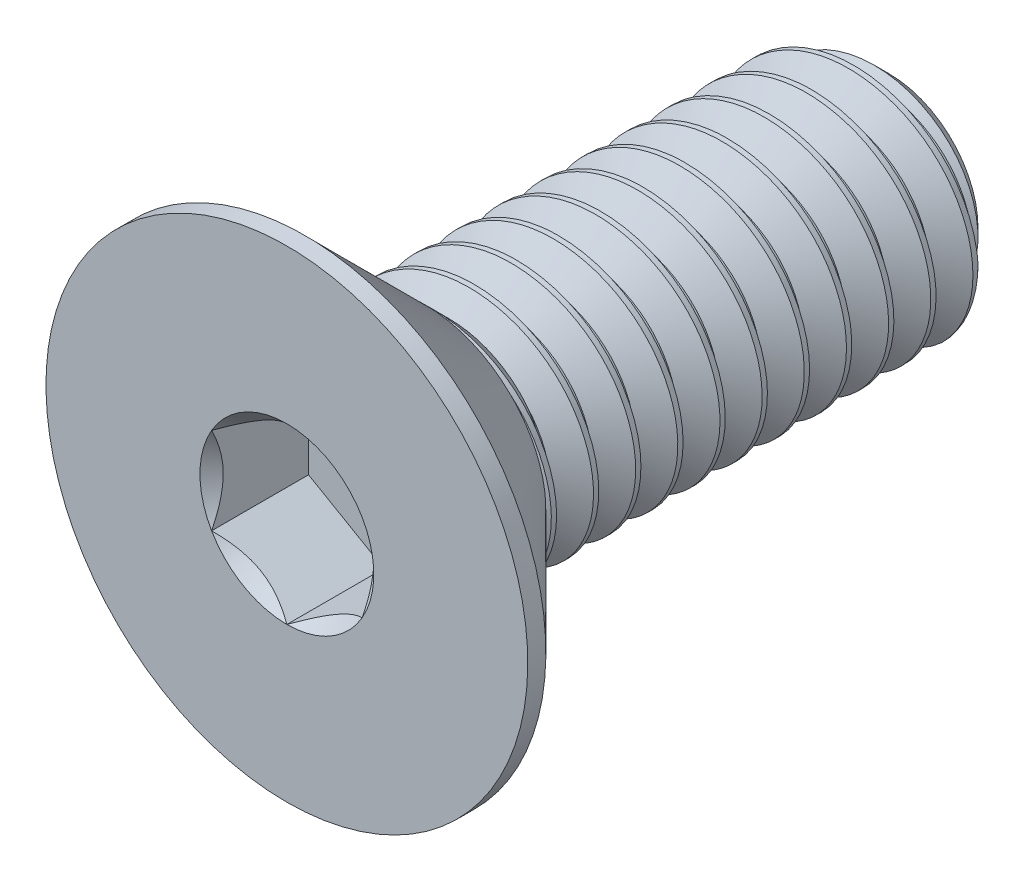
SolidWorks part; units mm, degrees
ref_plane "Front" through (0, 0, 0) normal (0, 0, 1) x (1, 0, 0)
ref_plane "Top" through (0, 0, 0) normal (0, 1, 0) x (1, 0, 0)
ref_plane "Right" through (0, 0, 0) normal (1, 0, 0) x (0, 0, -1)
sketch "Sketch1" plane through (0, 0, 0) normal (1, 0, 0) x (0, 0, -1)
  line L0 (0, 4) -> (0.3, 4) construction
  line L1 (0.3, 4) -> (2.3, 2) construction
  line L2 (0, 2) -> (10, 2)
  line L3 (10, 2) -> (10, 0)
  line L4 (10, 0) -> (0, 0)
  line L5 (0, 0) -> (0, 4) construction
  line L6 (0, 4) -> (0, -4) construction
  line L7 (10, 2) -> (10, -2) construction
  line L8 (0, -4) -> (0.3, -4) construction
  line L9 (0.3, -4) -> (2.3, -2) construction
  line L11 (0, 2) -> (0, 0)
  line L12 (2.3, 2) -> (2.3, 0) construction
revolve "Revolve1" add sketch "Sketch1" angle 360 mid plane about L4
sketch "Sketch3" plane through (0, 0, -10) normal (0, 0, -1) x (-1, 0, 0)
  circle A0 centre (0, 0) radius 2
curve "Helix/Spiral1" pitch 0.7 height 10 radius 2 centre (0, 0, -10) axis (0, 0, 1) start towards (0, 1, 0)
sketch "Sketch2" plane through (0, 0, 0) normal (1, 0, 0) x (0, 0, -1)
  line L0 (10, 2) -> (10.6125, 2)
  line L1 (10.6125, 2) -> (10.35, 1.5453)
  line L2 (10.35, 1.5453) -> (10.2625, 1.5453)
  line L3 (10.2625, 1.5453) -> (10, 2)
  line L4 (10.1312, 1.7727) -> (10.4812, 1.7727) construction
  dimension "D1" = 60
  dimension "D2" = 0.0875
  dimension "D3" = 0.35
chamfer "Chamfer1" distance 0.525 angle 45 1 edges at (0, 2, -10)
sweep "Cut-Sweep1" cut profiles "Sketch2" path "Helix/Spiral1"
sketch "Sketch7" plane through (0, 0, 0) normal (1, 0, 0) x (0, 0, -1)
  line L0 (0, 4) -> (0.3, 4) construction
  line L1 (0.3, 4) -> (2.3, 2) construction
  line L2 (0, 4) -> (0.3, 4)
  line L3 (0.3, 4) -> (2.3, 2)
  line L4 (2.3, 2) -> (2.3, 0) construction
  line L5 (2.3, 2) -> (2.3, 0)
  line L7 (0, 0) -> (0, 4) construction
  line L8 (0, 0) -> (0, 4)
  line L9 (0, 0) -> (2.3, 0)
  line L10 (4.4, 0) -> (-4.4, 0) construction
revolve "Revolve2" add sketch "Sketch7" angle 360 mid plane about L9
ref_plane "Plane1" through (0, 0, -2.3) normal (0, 0, 1) x (1, 0, 0)
sketch "Sketch8" plane through (0, 0, -2.3) normal (0, 0, 1) x (1, 0, 0)
  circle A0 centre (0, 0) radius 2
extrude "Boss-Extrude1" add sketch "Sketch8" against normal through all draft 45
sketch "Sketch5" plane through (0, 0, 0) normal (0, 0, 1) x (1, 0, 0)
  line L1 (1.25, -0.7217) -> (1.25, 0.7217)
  line L2 (1.25, 0.7217) -> (0, 1.4434)
  line L3 (0, 1.4434) -> (-1.25, 0.7217)
  line L4 (-1.25, 0.7217) -> (-1.25, -0.7217)
  line L5 (-1.25, -0.7217) -> (0, -1.4434)
  line L6 (0, -1.4434) -> (1.25, -0.7217)
  circle A0 centre (0, 0) radius 1.25 construction
  dimension "Hex" = 2.5
extrude "Cut-Extrude2" cut sketch "Sketch5" against normal blind 1.61
sketch "Sketch6" plane through (0, 0, 0) normal (0, 0, 1) x (1, 0, 0)
  circle A0 centre (0, 0) radius 1.4434
extrude "Cut-Extrude3" cut sketch "Sketch6" against normal blind 1.61 draft 45
sketch "Sketch9" [suppressed] plane through (0, 0, -1.5) normal (0, 0, 1) x (1, 0, 0)
  circle A1 centre (0, 0) radius 1.25
  circle A2 centre (0, 0) radius 1.25
  point P0 (0, 1.25)
  dimension "D1" = 0
extrude "Boss-Extrude2" [suppressed] add sketch "Sketch9" against normal offset from surface (3.5 mm away) 26 up to face at (0, 1.475, -10)
fillet "Fillet1" [suppressed] radius 0.4
sketch "Sketch10" plane through (0, 0, 0) normal (1, 0, 0) x (0, 0, -1)
  line L0 (10, 2) -> (10, -2) construction
  point P0 (8.95, -2)
  dimension "D1" = 1.05
equation "\"D3@Helix/Spiral1\" = \"Lg@Sketch1\""
equation "\"D2@Sketch2\" = \"D4@Helix/Spiral1\" * .125"
equation "\"D3@Sketch2\" = \"D4@Helix/Spiral1\" * .5"
equation "\"D1@Chamfer1\" = \"D4@Helix/Spiral1\" * .75"
equation "\"D1@Cut-Extrude2\" = \"Head Ht@Sketch1\" * .7"
equation "\"D1@Sketch10\" = \"D4@Helix/Spiral1\" * 1.5"
equation "\"D1@Cut-Extrude3\" = \"D1@Cut-Extrude2\""
equation "\"D1@Fillet1\" = \"Dia@Sketch1\" * .1"
